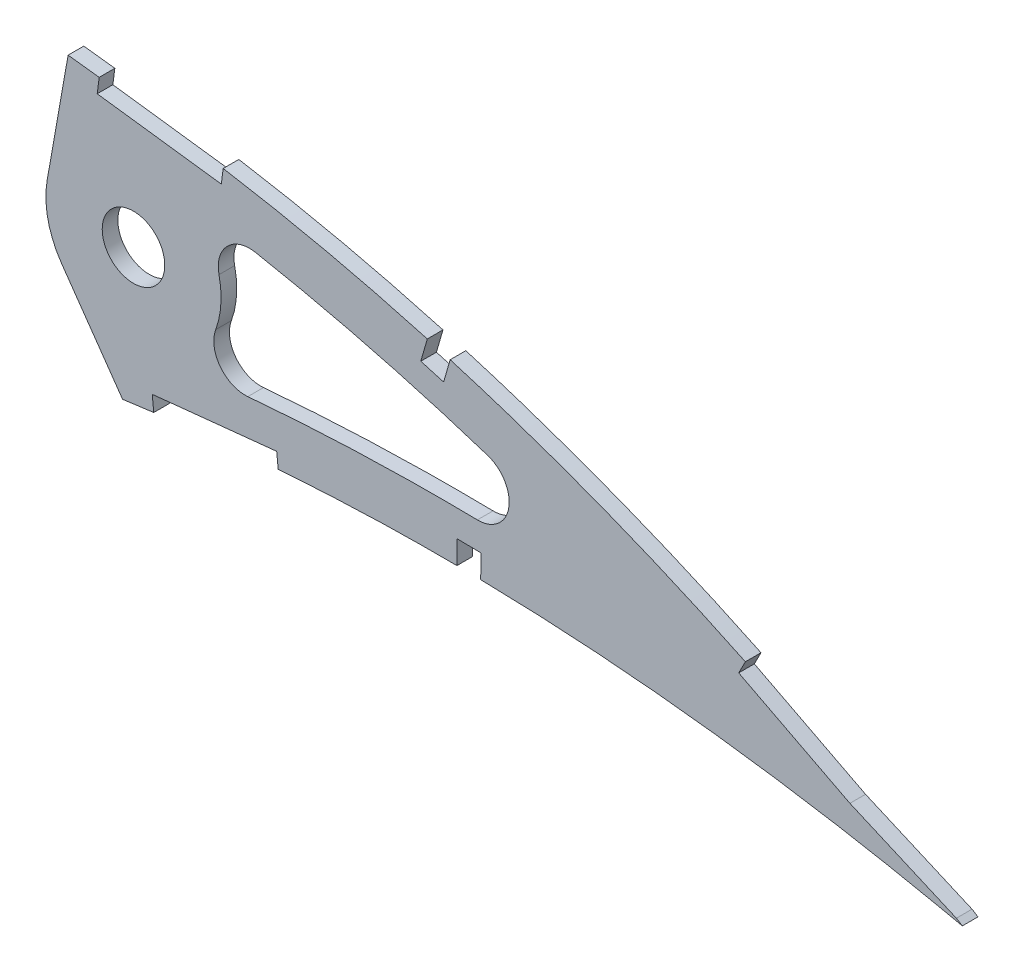
SolidWorks part; units mm, degrees
material "Pine"
ref_plane "Front Plane" through (0, 0, 0) normal (0, 0, 1) x (1, 0, 0)
ref_plane "Top Plane" through (0, 0, 0) normal (0, 1, 0) x (1, 0, 0)
ref_plane "Right Plane" through (0, 0, 0) normal (1, 0, 0) x (0, 0, -1)
curve "Curve1"
  spline degree 3 poles (554.3197, 0.8642, 0) (554.2772, 0.8904, 0) (554.1075, 0.9953, 0) (553.7252, 1.2298, 0) (553.0885, 1.6204, 0) (552.1972, 2.1644, 0) (551.0519, 2.8603, 0) (549.6522, 3.7033, 0) (547.9988, 4.6906, 0) (546.0922, 5.8176, 0) (543.9326, 7.0789, 0) (541.5207, 8.4695, 0) (538.8569, 9.9815, 0) (535.942, 11.6087, 0) (532.7772, 13.3434, 0) (529.3631, 15.1777, 0) (525.7007, 17.1023, 0) (521.7917, 19.109, 0) (517.6366, 21.1866, 0) (513.2374, 23.3265, 0) (508.5956, 25.518, 0) (503.7128, 27.7495, 0) (498.5918, 30.0118, 0) (493.234, 32.2909, 0) (487.6424, 34.577, 0) (481.8195, 36.8569, 0) (475.7686, 39.1203, 0) (469.4922, 41.3526, 0) (462.9949, 43.5439, 0) (456.2798, 45.6802, 0) (449.3518, 47.7496, 0) (442.2149, 49.739, 0) (434.875, 51.6379, 0) (427.3368, 53.4327, 0) (419.6066, 55.1112, 0) (411.6907, 56.6635, 0) (403.5957, 58.0739, 0) (395.344, 59.3415, 0) (387.0683, 60.3958, 0) (378.8096, 61.4299, 0) (370.5633, 62.4014, 0) (362.2161, 63.3317, 0) (353.7762, 64.2156, 0) (345.252, 65.0503, 0) (336.6519, 65.8323, 0) (327.9851, 66.5592, 0) (319.2598, 67.227, 0) (310.4852, 67.8346, 0) (301.6702, 68.3766, 0) (292.8239, 68.8527, 0) (283.9555, 69.2595, 0) (275.0741, 69.5943, 0) (266.1892, 69.8549, 0) (257.3099, 70.039, 0) (248.446, 70.1454, 0) (239.6066, 70.171, 0) (230.8014, 70.1156, 0) (222.0395, 69.9772, 0) (213.3305, 69.7538, 0) (204.6838, 69.4452, 0) (196.1087, 69.0513, 0) (187.6145, 68.5689, 0) (179.2105, 68.0012, 0) (170.9059, 67.3456, 0) (162.7101, 66.6021, 0) (154.6315, 65.7736, 0) (146.6791, 64.8581, 0) (138.8614, 63.858, 0) (131.1871, 62.7754, 0) (123.6647, 61.6096, 0) (116.3022, 60.3641, 0) (109.1077, 59.04, 0) (102.0887, 57.6413, 0) (95.2529, 56.1683, 0) (88.6074, 54.6255, 0) (82.1593, 53.0155, 0) (75.9155, 51.3413, 0) (69.8822, 49.607, 0) (64.0656, 47.8163, 0) (58.4725, 45.9714, 0) (53.107, 44.0792, 0) (47.9758, 42.141, 0) (43.0829, 40.1629, 0) (38.4338, 38.1474, 0) (34.0322, 36.1008, 0) (29.883, 34.0255, 0) (25.9891, 31.9271, 0) (22.3545, 29.809, 0) (18.9827, 27.675, 0) (15.875, 25.5306, 0) (13.0358, 23.3771, 0) (10.4661, 21.22, 0) (8.1674, 19.0625, 0) (6.143, 16.9061, 0) (4.3929, 14.7547, 0) (2.9194, 12.6099, 0) (1.7228, 10.4738, 0) (0.8056, 8.3479, 0) (0.1671, 6.2334, 0) (-0.1824, 4.1334, 0) (-0.2694, 2.0463, 0) (-0.0897, 0.6811, 0) (0, 0, 0) knots 0 0 0 0 0.000254 0.001015 0.002283 0.004057 0.006331 0.009105 0.012374 0.016134 0.02038 0.025106 0.030306 0.035972 0.0421 0.048678 0.055702 0.06316 0.071046 0.07935 0.088063 0.097176 0.106678 0.116562 0.126814 0.137428 0.148394 0.1597 0.171338 0.183298 0.19557 0.208144 0.221012 0.234162 0.247587 0.261277 0.275223 0.289414 0.303771 0.317689 0.331784 0.34604 0.360444 0.374983 0.38964 0.404403 0.419257 0.434187 0.449177 0.464215 0.479284 0.49437 0.509458 0.524532 0.539579 0.554583 0.56953 0.584403 0.599191 0.613877 0.628447 0.642889 0.657186 0.671326 0.685294 0.699078 0.712665 0.726043 0.739198 0.752118 0.764792 0.777208 0.789356 0.801224 0.812804 0.824083 0.835055 0.84571 0.856038 0.866034 0.875689 0.884998 0.893953 0.902553 0.910789 0.918661 0.926166 0.933303 0.940071 0.946475 0.952518 0.958205 0.963547 0.968557 0.97325 0.977651 0.981787 0.985694 0.989415 0.993001 0.996508 1 1 1 1
curve "Curve2"
  spline degree 3 poles (0, 0, 0) (0.1423, -0.672, 0) (0.4277, -2.019, 0) (1.203, -3.9582, 0) (2.2282, -5.8223, 0) (3.5249, -7.6064, 0) (5.0845, -9.31, 0) (6.9036, -10.9348, 0) (8.9803, -12.4801, 0) (11.3119, -13.945, 0) (13.8951, -15.3312, 0) (16.7269, -16.6378, 0) (19.8048, -17.8643, 0) (23.1254, -19.0092, 0) (26.6846, -20.0741, 0) (30.4791, -21.0566, 0) (34.5045, -21.9578, 0) (38.7571, -22.7757, 0) (43.232, -23.5109, 0) (47.9248, -24.1631, 0) (52.8305, -24.7327, 0) (57.9444, -25.2185, 0) (63.2614, -25.6215, 0) (68.7762, -25.942, 0) (74.4834, -26.1811, 0) (80.3777, -26.3377, 0) (86.4531, -26.4144, 0) (92.7043, -26.4123, 0) (99.1251, -26.3308, 0) (105.71, -26.1745, 0) (112.4527, -25.9423, 0) (119.3471, -25.6371, 0) (126.387, -25.2619, 0) (133.5661, -24.818, 0) (140.8781, -24.3074, 0) (148.3166, -23.7341, 0) (155.8748, -23.0997, 0) (163.5462, -22.4077, 0) (171.324, -21.6617, 0) (179.2015, -20.864, 0) (187.1716, -20.0183, 0) (195.2274, -19.1275, 0) (203.3619, -18.1963, 0) (211.5677, -17.2262, 0) (219.8379, -16.223, 0) (228.1647, -15.1885, 0) (236.5412, -14.1266, 0) (244.9597, -13.0425, 0) (253.4125, -11.9359, 0) (261.8924, -10.8148, 0) (270.3912, -9.6781, 0) (278.9016, -8.5319, 0) (287.4156, -7.3796, 0) (295.925, -6.2216, 0) (304.4222, -5.0626, 0) (312.8995, -3.9059, 0) (321.3485, -2.7516, 0) (329.7616, -1.6054, 0) (338.1302, -0.4672, 0) (346.4467, 0.6607, 0) (354.7031, 1.775, 0) (362.8916, 2.8743, 0) (371.0037, 3.9578, 0) (379.0314, 5.0259, 0) (386.8463, 6.0463, 0) (394.4281, 7.0733, 0) (401.8022, 7.9152, 0) (409.0845, 8.6338, 0) (416.2825, 9.2229, 0) (423.3877, 9.6911, 0) (430.3918, 10.0417, 0) (437.2865, 10.2795, 0) (444.0631, 10.4116, 0) (450.7132, 10.4414, 0) (457.2276, 10.3785, 0) (463.598, 10.2277, 0) (469.8153, 9.9961, 0) (475.8709, 9.6912, 0) (481.7563, 9.3216, 0) (487.4626, 8.8925, 0) (492.9818, 8.4141, 0) (498.3055, 7.8933, 0) (503.4254, 7.336, 0) (508.334, 6.7541, 0) (513.0236, 6.1512, 0) (517.4871, 5.5374, 0) (521.7172, 4.9187, 0) (525.7074, 4.3032, 0) (529.4512, 3.6966, 0) (532.9427, 3.1071, 0) (536.1764, 2.5402, 0) (539.1467, 2.0013, 0) (541.8495, 1.4973, 0) (544.2794, 1.0307, 0) (546.4331, 0.6092, 0) (548.3068, 0.2346, 0) (549.8976, -0.0878, 0) (551.2027, -0.3567, 0) (552.2202, -0.5677, 0) (552.948, -0.7211, 0) (553.3854, -0.8124, 0) (553.5798, -0.8538, 0) (553.6283, -0.8642, 0) knots 0 0 0 0 0.003638 0.007293 0.011028 0.014901 0.018963 0.023258 0.027821 0.032679 0.037853 0.043362 0.049215 0.055422 0.061989 0.068918 0.076211 0.083868 0.091887 0.100266 0.109 0.118085 0.127515 0.137285 0.147388 0.157816 0.168563 0.179619 0.190977 0.202627 0.21456 0.226767 0.239236 0.251959 0.264924 0.27812 0.291536 0.30516 0.318981 0.332985 0.347163 0.361499 0.375981 0.390597 0.405333 0.420175 0.43511 0.450124 0.465203 0.480333 0.495501 0.51069 0.525887 0.541078 0.556247 0.571382 0.586466 0.601485 0.616424 0.631269 0.646007 0.660621 0.675098 0.689423 0.703582 0.716908 0.730009 0.742952 0.755726 0.76832 0.780724 0.792927 0.804916 0.816679 0.828204 0.839475 0.850481 0.861208 0.871639 0.881763 0.891564 0.901027 0.910139 0.918884 0.927249 0.935221 0.942785 0.949928 0.956638 0.962904 0.968712 0.974054 0.978918 0.983297 0.98718 0.990561 0.993433 0.995791 0.99763 0.998946 0.999737 1 1 1 1
sketch "Sketch1" plane through (0, 0, 0) normal (0, 0, 1) x (1, 0, 0)
  line L28 (0, 63.5) -> (-23.1981, 63.5) construction
  line L39 (379.9183, -27.3345) -> (379.9183, 27.3345) construction
  line L40 (368.4067, 59.4277) -> (353.2793, 2.9714) construction
  line L41 (537.5238, 0.838) -> (542.0214, -1.9404)
  line L42 (536.8534, -0.838) -> (542.0214, -1.9404)
  circle A0 centre (68.58, 6.35) radius 9.525 construction
  circle A1 centre (246.38, 6.35) radius 9.525 construction
  spline S3 degree 3 poles (0, 0) (0.138, -0.6516) (0.4147, -1.9578) (1.1665, -3.8383) (2.1607, -5.6459) (3.4181, -7.3759) (4.9305, -9.0279) (6.6944, -10.6035) (8.7082, -12.1019) (10.9692, -13.5225) (13.4741, -14.8667) (16.2201, -16.1336) (19.2047, -17.323) (22.4247, -18.4332) (25.8761, -19.4659) (29.5556, -20.4185) (33.4591, -21.2925) (37.5827, -22.0856) (41.9221, -22.7985) (46.4726, -23.431) (51.2297, -23.9833) (56.1887, -24.4544) (61.3446, -24.8452) (66.6923, -25.156) (72.2266, -25.3878) (77.9422, -25.5397) (83.8336, -25.6141) (89.8954, -25.612) (96.1216, -25.533) (102.507, -25.3814) (109.0454, -25.1563) (115.7309, -24.8603) (122.5575, -24.4965) (129.5191, -24.066) (136.6095, -23.5709) (143.8226, -23.015) (151.1518, -22.3997) (158.5908, -21.7287) (166.1329, -21.0053) (173.7717, -20.2318) (181.5003, -19.4118) (189.312, -18.5479) (197.2, -17.6449) (205.1572, -16.7043) (213.1768, -15.7315) (221.2513, -14.7283) (229.374, -13.6986) (237.5374, -12.6473) (245.7341, -11.5743) (253.957, -10.4871) (262.1983, -9.3849) (270.4508, -8.2734) (278.7069, -7.156) (286.9584, -6.033) (295.1983, -4.9092) (303.4187, -3.7876) (311.6117, -2.6683) (319.7698, -1.5568) (327.8848, -0.4531) (335.9493, 0.6407) (343.9556, 1.7212) (351.896, 2.7872) (359.7623, 3.8379) (367.5468, 4.8736) (375.1249, 5.8631) (382.4769, 6.859) (389.6276, 7.6754) (396.6892, 8.3722) (403.6691, 8.9435) (410.559, 9.3975) (417.3509, 9.7374) (424.0367, 9.968) (430.608, 10.0961) (437.0566, 10.1251) (443.3736, 10.064) (449.5509, 9.9178) (455.5799, 9.6932) (461.4521, 9.3976) (467.1591, 9.0391) (472.6925, 8.6231) (478.0445, 8.1591) (483.2068, 7.6541) (488.1716, 7.1138) (492.9315, 6.5494) (497.479, 5.9648) (501.8072, 5.3696) (505.9092, 4.7697) (509.7784, 4.1728) (513.4088, 3.5846) (516.7946, 3.013) (519.9303, 2.4632) (522.8106, 1.9407) (525.4315, 1.4519) (527.7877, 0.9995) (529.8762, 0.5907) (531.6931, 0.2275) (533.2357, -0.0851) (534.5012, -0.3459) (535.4879, -0.5505) (536.1937, -0.6992) (536.6178, -0.7878) (536.8063, -0.828) (536.8534, -0.838) knots 0 0 0 0 0.003638 0.007293 0.011028 0.014901 0.018963 0.023258 0.027821 0.032679 0.037853 0.043362 0.049215 0.055422 0.061989 0.068918 0.076211 0.083868 0.091887 0.100266 0.109 0.118085 0.127515 0.137285 0.147388 0.157816 0.168563 0.179619 0.190977 0.202627 0.21456 0.226767 0.239236 0.251959 0.264924 0.27812 0.291536 0.30516 0.318981 0.332985 0.347163 0.361499 0.375981 0.390597 0.405333 0.420175 0.43511 0.450124 0.465203 0.480333 0.495501 0.51069 0.525887 0.541078 0.556247 0.571382 0.586466 0.601485 0.616424 0.631269 0.646007 0.660621 0.675098 0.689423 0.703582 0.716908 0.730009 0.742952 0.755726 0.76832 0.780724 0.792927 0.804916 0.816679 0.828204 0.839475 0.850481 0.861208 0.871639 0.881763 0.891564 0.901027 0.910139 0.918884 0.927249 0.935221 0.942785 0.949928 0.956638 0.962904 0.968712 0.974054 0.978918 0.983297 0.98718 0.990561 0.993433 0.995791 0.99763 0.998946 0.999737 1 1 1 1
  spline S6 degree 3 poles (537.5238, 0.838) (537.4826, 0.8635) (537.3181, 0.9651) (536.9473, 1.1925) (536.3299, 1.5713) (535.4656, 2.0988) (534.3551, 2.7737) (532.9977, 3.5911) (531.3944, 4.5485) (529.5456, 5.6413) (527.4514, 6.8644) (525.1126, 8.2129) (522.5295, 9.6791) (519.703, 11.2569) (516.6341, 12.9391) (513.3234, 14.7178) (509.772, 16.5841) (505.9814, 18.53) (501.9522, 20.5446) (497.6863, 22.6197) (493.1852, 24.7448) (488.4503, 26.9087) (483.4845, 29.1025) (478.289, 31.3125) (472.8669, 33.5293) (467.2204, 35.7401) (461.3528, 37.9349) (455.2666, 40.0996) (448.9661, 42.2246) (442.4545, 44.296) (435.7364, 46.3028) (428.8157, 48.2319) (421.6983, 50.0733) (414.3885, 51.8137) (406.8926, 53.4414) (399.2165, 54.9466) (391.3668, 56.3143) (383.365, 57.5434) (375.3401, 58.5658) (367.3317, 59.5686) (359.3352, 60.5106) (351.241, 61.4127) (343.0568, 62.2698) (334.7908, 63.0793) (326.4514, 63.8376) (318.0471, 64.5425) (309.5862, 65.19) (301.0775, 65.7792) (292.5296, 66.3048) (283.9513, 66.7665) (275.3516, 67.161) (266.7393, 67.4856) (258.1236, 67.7383) (249.5134, 67.9168) (240.9181, 68.0199) (232.3465, 68.0449) (223.8081, 67.9911) (215.3117, 67.8569) (206.8666, 67.6403) (198.4819, 67.341) (190.1666, 66.959) (181.9298, 66.4913) (173.7804, 65.9407) (165.7275, 65.305) (157.78, 64.584) (149.9461, 63.7807) (142.2347, 62.8929) (134.6539, 61.9231) (127.2121, 60.8733) (119.9176, 59.7429) (112.7783, 58.535) (105.8017, 57.2511) (98.9954, 55.8947) (92.3667, 54.4664) (85.9226, 52.9703) (79.6699, 51.4091) (73.6153, 49.7857) (67.7648, 48.1039) (62.1244, 46.3675) (56.7008, 44.5785) (51.4979, 42.7436) (46.5222, 40.8641) (41.7775, 38.9459) (37.2693, 36.9916) (33.0011, 35.007) (28.9776, 32.9945) (25.2017, 30.9597) (21.6772, 28.9058) (18.4075, 26.8364) (15.394, 24.757) (12.6408, 22.6688) (10.1489, 20.577) (7.9199, 18.4849) (5.9569, 16.3939) (4.2598, 14.3076) (2.831, 12.2278) (1.6706, 10.1565) (0.7812, 8.095) (0.162, 6.0445) (-0.1769, 4.0082) (-0.2612, 1.9843) (-0.087, 0.6604) (0, 0) knots 0 0 0 0 0.000254 0.001015 0.002283 0.004057 0.006331 0.009105 0.012374 0.016134 0.02038 0.025106 0.030306 0.035972 0.0421 0.048678 0.055702 0.06316 0.071046 0.07935 0.088063 0.097176 0.106678 0.116562 0.126814 0.137428 0.148394 0.1597 0.171338 0.183298 0.19557 0.208144 0.221012 0.234162 0.247587 0.261277 0.275223 0.289414 0.303771 0.317689 0.331784 0.34604 0.360444 0.374983 0.38964 0.404403 0.419257 0.434187 0.449177 0.464215 0.479284 0.49437 0.509458 0.524532 0.539579 0.554583 0.56953 0.584403 0.599191 0.613877 0.628447 0.642889 0.657186 0.671326 0.685294 0.699078 0.712665 0.726043 0.739198 0.752118 0.764792 0.777208 0.789356 0.801224 0.812804 0.824083 0.835055 0.84571 0.856038 0.866034 0.875689 0.884998 0.893953 0.902553 0.910789 0.918661 0.926166 0.933303 0.940071 0.946475 0.952518 0.958205 0.963547 0.968557 0.97325 0.977651 0.981787 0.985694 0.989415 0.993001 0.996508 1 1 1 1
  point P10 (78.5929, 16.5948)
  point P11 (227.8303, 32.4941)
  dimension "D2" = 19.05
  dimension "D18" = 177.8
  dimension "D3" = 15
  dimension "D5" = 63.5
  dimension "D7" = 57.15
  dimension "D12" = 57.15
  dimension "D17" = 68.58
extrude "Boss-Extrude1" add sketch "Sketch1" along normal blind 3.175
sketch "Sketch4" plane through (0, 0, 0) normal (0, 0, -1) x (-1, 0, 0)
  line L0 (-356.287, 36.32) -> (-360.5267, 60.365)
  line L1 (-359.2323, 23.0344) -> (-371.5795, 5.4008)
  line L2 (-373.7968, 33.2326) -> (-412.6852, 33.2326)
  circle A0 centre (-373.7968, 33.2326) radius 17.78
  circle A1 centre (-373.7968, 33.2326) radius 6.35
  spline S0 degree 3 poles (-1632.0302, 1674.0962) (-565.4284, -22.6918) (-552.7247, -8.4851) (-536.9473, 1.1925) (-536.3299, 1.5713) (-535.4656, 2.0988) (-534.3551, 2.7737) (-532.9977, 3.5911) (-531.3944, 4.5485) (-529.5456, 5.6413) (-527.4514, 6.8644) (-525.1126, 8.2129) (-522.5295, 9.6791) (-519.703, 11.2569) (-516.6341, 12.9391) (-513.3234, 14.7178) (-509.772, 16.5841) (-505.9814, 18.53) (-501.9522, 20.5446) (-497.6863, 22.6197) (-493.1852, 24.7448) (-488.4503, 26.9087) (-483.4845, 29.1025) (-478.289, 31.3125) (-472.8669, 33.5293) (-467.2204, 35.7401) (-461.3528, 37.9349) (-455.2666, 40.0996) (-448.9661, 42.2246) (-442.4545, 44.296) (-435.7364, 46.3028) (-428.8157, 48.2319) (-421.6983, 50.0733) (-414.3885, 51.8137) (-406.8926, 53.4414) (-399.2165, 54.9466) (-391.3668, 56.3143) (-383.365, 57.5434) (-375.3401, 58.5658) (-367.3317, 59.5686) (-359.3352, 60.5106) (-351.241, 61.4127) (-343.0568, 62.2698) (-334.7908, 63.0793) (-326.4514, 63.8376) (-318.0471, 64.5425) (-309.5862, 65.19) (-301.0775, 65.7792) (-292.5296, 66.3048) (-283.9513, 66.7665) (-275.3516, 67.161) (-266.7393, 67.4856) (-258.1236, 67.7383) (-249.5134, 67.9168) (-240.9181, 68.0199) (-232.3465, 68.0449) (-223.8081, 67.9911) (-215.3117, 67.8569) (-206.8666, 67.6403) (-198.4819, 67.341) (-190.1666, 66.959) (-181.9298, 66.4913) (-173.7804, 65.9407) (-165.7275, 65.305) (-157.78, 64.584) (-149.9461, 63.7807) (-142.2347, 62.8929) (-134.6539, 61.9231) (-127.2121, 60.8733) (-119.9176, 59.7429) (-112.7783, 58.535) (-105.8017, 57.2511) (-98.9954, 55.8947) (-92.3667, 54.4664) (-85.9226, 52.9703) (-79.6699, 51.4091) (-73.6153, 49.7857) (-67.7648, 48.1039) (-62.1244, 46.3675) (-56.7008, 44.5785) (-51.4979, 42.7436) (-46.5222, 40.8641) (-41.7775, 38.9459) (-37.2693, 36.9916) (-33.0011, 35.007) (-28.9776, 32.9945) (-25.2017, 30.9597) (-21.6772, 28.9058) (-18.4075, 26.8364) (-15.394, 24.757) (-12.6408, 22.6688) (-10.1489, 20.577) (-7.9199, 18.4849) (-5.9569, 16.3939) (-4.2598, 14.3076) (-2.831, 12.2278) (-1.6706, 10.1565) (-0.7812, 8.095) (-0.162, 6.0445) (0.1769, 4.0082) (1.1707, -19.8347) (-66.7598, -38.6935) (1990.434, -189.4699) knots -0.094882 -0.094882 -0.094882 -0.094882 0.000254 0.001015 0.002283 0.004057 0.006331 0.009105 0.012374 0.016134 0.02038 0.025106 0.030306 0.035972 0.0421 0.048678 0.055702 0.06316 0.071046 0.07935 0.088063 0.097176 0.106678 0.116562 0.126814 0.137428 0.148394 0.1597 0.171338 0.183298 0.19557 0.208144 0.221012 0.234162 0.247587 0.261277 0.275223 0.289414 0.303771 0.317689 0.331784 0.34604 0.360444 0.374983 0.38964 0.404403 0.419257 0.434187 0.449177 0.464215 0.479284 0.49437 0.509458 0.524532 0.539579 0.554583 0.56953 0.584403 0.599191 0.613877 0.628447 0.642889 0.657186 0.671326 0.685294 0.699078 0.712665 0.726043 0.739198 0.752118 0.764792 0.777208 0.789356 0.801224 0.812804 0.824083 0.835055 0.84571 0.856038 0.866034 0.875689 0.884998 0.893953 0.902553 0.910789 0.918661 0.926166 0.933303 0.940071 0.946475 0.952518 0.958205 0.963547 0.968557 0.97325 0.977651 0.981787 0.985694 0.989415 0.993001 0.996508 1.114113 1.114113 1.114113 1.114113 only from (-537.5238, 0.838) to (0, 0) construction
  spline S1 degree 3 poles (1940.1203, -483.4322) (-49.9299, 58.7424) (7.7069, 18.357) (-1.1665, -3.8383) (-2.1607, -5.6459) (-3.4181, -7.3759) (-4.9305, -9.0279) (-6.6944, -10.6035) (-8.7082, -12.1019) (-10.9692, -13.5225) (-13.4741, -14.8667) (-16.2201, -16.1336) (-19.2047, -17.323) (-22.4247, -18.4332) (-25.8761, -19.4659) (-29.5556, -20.4185) (-33.4591, -21.2925) (-37.5827, -22.0856) (-41.9221, -22.7985) (-46.4726, -23.431) (-51.2297, -23.9833) (-56.1887, -24.4544) (-61.3446, -24.8452) (-66.6923, -25.156) (-72.2266, -25.3878) (-77.9422, -25.5397) (-83.8336, -25.6141) (-89.8954, -25.612) (-96.1216, -25.533) (-102.507, -25.3814) (-109.0454, -25.1563) (-115.7309, -24.8603) (-122.5575, -24.4965) (-129.5191, -24.066) (-136.6095, -23.5709) (-143.8226, -23.015) (-151.1518, -22.3997) (-158.5908, -21.7287) (-166.1329, -21.0053) (-173.7717, -20.2318) (-181.5003, -19.4118) (-189.312, -18.5479) (-197.2, -17.6449) (-205.1572, -16.7043) (-213.1768, -15.7315) (-221.2513, -14.7283) (-229.374, -13.6986) (-237.5374, -12.6473) (-245.7341, -11.5743) (-253.957, -10.4871) (-262.1983, -9.3849) (-270.4508, -8.2734) (-278.7069, -7.156) (-286.9584, -6.033) (-295.1983, -4.9092) (-303.4187, -3.7876) (-311.6117, -2.6683) (-319.7698, -1.5568) (-327.8848, -0.4531) (-335.9493, 0.6407) (-343.9556, 1.7212) (-351.896, 2.7872) (-359.7623, 3.8379) (-367.5468, 4.8736) (-375.1249, 5.8631) (-382.4769, 6.859) (-389.6276, 7.6754) (-396.6892, 8.3722) (-403.6691, 8.9435) (-410.559, 9.3975) (-417.3509, 9.7374) (-424.0367, 9.968) (-430.608, 10.0961) (-437.0566, 10.1251) (-443.3736, 10.064) (-449.5509, 9.9178) (-455.5799, 9.6932) (-461.4521, 9.3976) (-467.1591, 9.0391) (-472.6925, 8.6231) (-478.0445, 8.1591) (-483.2068, 7.6541) (-488.1716, 7.1138) (-492.9315, 6.5494) (-497.479, 5.9648) (-501.8072, 5.3696) (-505.9092, 4.7697) (-509.7784, 4.1728) (-513.4088, 3.5846) (-516.7946, 3.013) (-519.9303, 2.4632) (-522.8106, 1.9407) (-525.4315, 1.4519) (-527.7877, 0.9995) (-529.8762, 0.5907) (-531.6931, 0.2275) (-533.2357, -0.0851) (-534.5012, -0.3459) (-535.4879, -0.5505) (-536.1937, -0.6992) (-552.4366, -4.0895) (-567.1821, -13.3973) (-997.8539, 1944.6618) knots -0.119141 -0.119141 -0.119141 -0.119141 0.003638 0.007293 0.011028 0.014901 0.018963 0.023258 0.027821 0.032679 0.037853 0.043362 0.049215 0.055422 0.061989 0.068918 0.076211 0.083868 0.091887 0.100266 0.109 0.118085 0.127515 0.137285 0.147388 0.157816 0.168563 0.179619 0.190977 0.202627 0.21456 0.226767 0.239236 0.251959 0.264924 0.27812 0.291536 0.30516 0.318981 0.332985 0.347163 0.361499 0.375981 0.390597 0.405333 0.420175 0.43511 0.450124 0.465203 0.480333 0.495501 0.51069 0.525887 0.541078 0.556247 0.571382 0.586466 0.601485 0.616424 0.631269 0.646007 0.660621 0.675098 0.689423 0.703582 0.716908 0.730009 0.742952 0.755726 0.76832 0.780724 0.792927 0.804916 0.816679 0.828204 0.839475 0.850481 0.861208 0.871639 0.881763 0.891564 0.901027 0.910139 0.918884 0.927249 0.935221 0.942785 0.949928 0.956638 0.962904 0.968712 0.974054 0.978918 0.983297 0.98718 0.990561 0.993433 0.995791 0.99763 0.998946 0.999737 1.088404 1.088404 1.088404 1.088404 only from (0, 0) to (-536.8534, -0.838) construction
  spline S2 degree 3 poles (-537.5238, 0.838) (-537.4826, 0.8635) (-537.3181, 0.9651) (-536.9473, 1.1925) (-536.3299, 1.5713) (-535.4656, 2.0988) (-534.3551, 2.7737) (-532.9977, 3.5911) (-531.3944, 4.5485) (-529.5456, 5.6413) (-527.4514, 6.8644) (-525.1126, 8.2129) (-522.5295, 9.6791) (-519.703, 11.2569) (-516.6341, 12.9391) (-513.3234, 14.7178) (-509.772, 16.5841) (-505.9814, 18.53) (-501.9522, 20.5446) (-497.6863, 22.6197) (-493.1852, 24.7448) (-488.4503, 26.9087) (-483.4845, 29.1025) (-478.289, 31.3125) (-472.8669, 33.5293) (-467.2204, 35.7401) (-461.3528, 37.9349) (-455.2666, 40.0996) (-448.9661, 42.2246) (-442.4545, 44.296) (-435.7364, 46.3028) (-428.8157, 48.2319) (-421.6983, 50.0733) (-414.3885, 51.8137) (-406.8926, 53.4414) (-399.2165, 54.9466) (-391.3668, 56.3143) (-383.365, 57.5434) (-375.3401, 58.5658) (-367.3317, 59.5686) (-359.3352, 60.5106) (-351.241, 61.4127) (-343.0568, 62.2698) (-334.7908, 63.0793) (-326.4514, 63.8376) (-318.0471, 64.5425) (-309.5862, 65.19) (-301.0775, 65.7792) (-292.5296, 66.3048) (-283.9513, 66.7665) (-275.3516, 67.161) (-266.7393, 67.4856) (-258.1236, 67.7383) (-249.5134, 67.9168) (-240.9181, 68.0199) (-232.3465, 68.0449) (-223.8081, 67.9911) (-215.3117, 67.8569) (-206.8666, 67.6403) (-198.4819, 67.341) (-190.1666, 66.959) (-181.9298, 66.4913) (-173.7804, 65.9407) (-165.7275, 65.305) (-157.78, 64.584) (-149.9461, 63.7807) (-142.2347, 62.8929) (-134.6539, 61.9231) (-127.2121, 60.8733) (-119.9176, 59.7429) (-112.7783, 58.535) (-105.8017, 57.2511) (-98.9954, 55.8947) (-92.3667, 54.4664) (-85.9226, 52.9703) (-79.6699, 51.4091) (-73.6153, 49.7857) (-67.7648, 48.1039) (-62.1244, 46.3675) (-56.7008, 44.5785) (-51.4979, 42.7436) (-46.5222, 40.8641) (-41.7775, 38.9459) (-37.2693, 36.9916) (-33.0011, 35.007) (-28.9776, 32.9945) (-25.2017, 30.9597) (-21.6772, 28.9058) (-18.4075, 26.8364) (-15.394, 24.757) (-12.6408, 22.6688) (-10.1489, 20.577) (-7.9199, 18.4849) (-5.9569, 16.3939) (-4.2598, 14.3076) (-2.831, 12.2278) (-1.6706, 10.1565) (-0.7812, 8.095) (-0.162, 6.0445) (0.1769, 4.0082) (0.2612, 1.9843) (0.087, 0.6604) (0, 0) knots 0 0 0 0 0.000254 0.001015 0.002283 0.004057 0.006331 0.009105 0.012374 0.016134 0.02038 0.025106 0.030306 0.035972 0.0421 0.048678 0.055702 0.06316 0.071046 0.07935 0.088063 0.097176 0.106678 0.116562 0.126814 0.137428 0.148394 0.1597 0.171338 0.183298 0.19557 0.208144 0.221012 0.234162 0.247587 0.261277 0.275223 0.289414 0.303771 0.317689 0.331784 0.34604 0.360444 0.374983 0.38964 0.404403 0.419257 0.434187 0.449177 0.464215 0.479284 0.49437 0.509458 0.524532 0.539579 0.554583 0.56953 0.584403 0.599191 0.613877 0.628447 0.642889 0.657186 0.671326 0.685294 0.699078 0.712665 0.726043 0.739198 0.752118 0.764792 0.777208 0.789356 0.801224 0.812804 0.824083 0.835055 0.84571 0.856038 0.866034 0.875689 0.884998 0.893953 0.902553 0.910789 0.918661 0.926166 0.933303 0.940071 0.946475 0.952518 0.958205 0.963547 0.968557 0.97325 0.977651 0.981787 0.985694 0.989415 0.993001 0.996508 1 1 1 1
  spline S3 degree 3 poles (0, 0) (-0.138, -0.6516) (-0.4147, -1.9578) (-1.1665, -3.8383) (-2.1607, -5.6459) (-3.4181, -7.3759) (-4.9305, -9.0279) (-6.6944, -10.6035) (-8.7082, -12.1019) (-10.9692, -13.5225) (-13.4741, -14.8667) (-16.2201, -16.1336) (-19.2047, -17.323) (-22.4247, -18.4332) (-25.8761, -19.4659) (-29.5556, -20.4185) (-33.4591, -21.2925) (-37.5827, -22.0856) (-41.9221, -22.7985) (-46.4726, -23.431) (-51.2297, -23.9833) (-56.1887, -24.4544) (-61.3446, -24.8452) (-66.6923, -25.156) (-72.2266, -25.3878) (-77.9422, -25.5397) (-83.8336, -25.6141) (-89.8954, -25.612) (-96.1216, -25.533) (-102.507, -25.3814) (-109.0454, -25.1563) (-115.7309, -24.8603) (-122.5575, -24.4965) (-129.5191, -24.066) (-136.6095, -23.5709) (-143.8226, -23.015) (-151.1518, -22.3997) (-158.5908, -21.7287) (-166.1329, -21.0053) (-173.7717, -20.2318) (-181.5003, -19.4118) (-189.312, -18.5479) (-197.2, -17.6449) (-205.1572, -16.7043) (-213.1768, -15.7315) (-221.2513, -14.7283) (-229.374, -13.6986) (-237.5374, -12.6473) (-245.7341, -11.5743) (-253.957, -10.4871) (-262.1983, -9.3849) (-270.4508, -8.2734) (-278.7069, -7.156) (-286.9584, -6.033) (-295.1983, -4.9092) (-303.4187, -3.7876) (-311.6117, -2.6683) (-319.7698, -1.5568) (-327.8848, -0.4531) (-335.9493, 0.6407) (-343.9556, 1.7212) (-351.896, 2.7872) (-359.7623, 3.8379) (-367.5468, 4.8736) (-375.1249, 5.8631) (-382.4769, 6.859) (-389.6276, 7.6754) (-396.6892, 8.3722) (-403.6691, 8.9435) (-410.559, 9.3975) (-417.3509, 9.7374) (-424.0367, 9.968) (-430.608, 10.0961) (-437.0566, 10.1251) (-443.3736, 10.064) (-449.5509, 9.9178) (-455.5799, 9.6932) (-461.4521, 9.3976) (-467.1591, 9.0391) (-472.6925, 8.6231) (-478.0445, 8.1591) (-483.2068, 7.6541) (-488.1716, 7.1138) (-492.9315, 6.5494) (-497.479, 5.9648) (-501.8072, 5.3696) (-505.9092, 4.7697) (-509.7784, 4.1728) (-513.4088, 3.5846) (-516.7946, 3.013) (-519.9303, 2.4632) (-522.8106, 1.9407) (-525.4315, 1.4519) (-527.7877, 0.9995) (-529.8762, 0.5907) (-531.6931, 0.2275) (-533.2357, -0.0851) (-534.5012, -0.3459) (-535.4879, -0.5505) (-536.1937, -0.6992) (-536.6178, -0.7878) (-536.8063, -0.828) (-536.8534, -0.838) knots 0 0 0 0 0.003638 0.007293 0.011028 0.014901 0.018963 0.023258 0.027821 0.032679 0.037853 0.043362 0.049215 0.055422 0.061989 0.068918 0.076211 0.083868 0.091887 0.100266 0.109 0.118085 0.127515 0.137285 0.147388 0.157816 0.168563 0.179619 0.190977 0.202627 0.21456 0.226767 0.239236 0.251959 0.264924 0.27812 0.291536 0.30516 0.318981 0.332985 0.347163 0.361499 0.375981 0.390597 0.405333 0.420175 0.43511 0.450124 0.465203 0.480333 0.495501 0.51069 0.525887 0.541078 0.556247 0.571382 0.586466 0.601485 0.616424 0.631269 0.646007 0.660621 0.675098 0.689423 0.703582 0.716908 0.730009 0.742952 0.755726 0.76832 0.780724 0.792927 0.804916 0.816679 0.828204 0.839475 0.850481 0.861208 0.871639 0.881763 0.891564 0.901027 0.910139 0.918884 0.927249 0.935221 0.942785 0.949928 0.956638 0.962904 0.968712 0.974054 0.978918 0.983297 0.98718 0.990561 0.993433 0.995791 0.99763 0.998946 0.999737 1 1 1 1
  spline S4 degree 1 poles (-532.1841, -7.8057) (-10.0219, 1.7185) knots 0 0 1 1 construction
  spline S5 degree 1 poles (-10.0219, 1.7185) (-538.9729, 9.0984) knots 0 0 1 1 construction
  spline S6 degree 3 poles (-532.1841, -7.8057) (-532.035, -7.7136) (-531.7436, -7.5345) (-531.1023, -7.1412) (-530.0303, -6.4862) (-527.85, -5.1645) (-523.4829, -2.5651) (-514.6678, 2.5066) (-496.7411, 12.095) (-470.3238, 24.1396) (-442.9694, 33.791) (-420.6386, 39.9785) (-406.5149, 43.1961) (-395.1531, 45.3637) (-386.5599, 46.8051) (-378.0384, 47.9972) (-369.1749, 49.1011) (-360.4166, 50.162) (-348.6799, 51.484) (-328.147, 53.5808) (-298.749, 55.9238) (-263.4315, 57.6196) (-228.1119, 58.0844) (-192.8506, 57.171) (-157.7356, 54.6709) (-128.7085, 51.0365) (-105.7459, 46.987) (-88.7097, 43.306) (-71.9299, 38.8842) (-58.261, 34.4734) (-47.6305, 30.4115) (-39.8596, 27.063) (-32.3674, 23.3733) (-25.2794, 19.2928) (-18.8179, 14.7781) (-14.319, 10.6534) (-11.7187, 7.3378) (-10.6606, 5.4268) (-10.2382, 4.2645) (-10.0884, 3.6968) (-10.0101, 3.295) (-9.9553, 2.8496) (-9.9432, 2.5723) (-9.9453, 2.4518) (-9.9493, 2.3713) (-9.9688, 2.1598) (-9.9949, 1.9339) (-10.0132, 1.7875) (-10.0219, 1.7185) knots 0 0 0 0 0.000976 0.001952 0.003903 0.007807 0.015613 0.031226 0.062452 0.124904 0.187357 0.218583 0.249809 0.265422 0.281035 0.296648 0.312261 0.327874 0.343487 0.374713 0.437166 0.499618 0.56207 0.624522 0.686974 0.749427 0.780653 0.811879 0.843105 0.874331 0.889944 0.905557 0.92117 0.936783 0.952396 0.968009 0.975816 0.983623 0.987526 0.989477 0.991429 0.993381 0.995332 0.996308 0.997284 0.99826 0.998748 0.999236 0.999236 0.999236 0.999236
  spline S7 degree 3 poles (-10.0219, 1.7185) (-10.0361, 1.6529) (-10.0665, 1.5144) (-10.1157, 1.2979) (-10.1669, 1.0931) (-10.1938, 1.0009) (-10.2267, 0.9008) (-10.3197, 0.6625) (-10.5705, 0.1458) (-10.9157, -0.4199) (-11.7404, -1.469) (-13.2635, -2.8937) (-16.5705, -5.1355) (-21.8641, -7.6046) (-29.0738, -9.8943) (-36.7462, -11.652) (-44.6834, -12.9788) (-52.7844, -13.9626) (-63.7273, -14.8945) (-77.583, -15.4719) (-94.3476, -15.4772) (-111.1866, -14.9569) (-133.6938, -13.7131) (-161.8825, -11.3422) (-195.7357, -7.6685) (-229.6092, -3.472) (-263.4966, 1.0208) (-297.4142, 5.6457) (-325.6956, 9.51) (-345.5133, 12.184) (-356.8358, 13.6973) (-363.916, 14.6412) (-369.594, 15.387) (-373.812, 15.9419) (-378.0525, 16.5127) (-382.4211, 17.0728) (-386.7861, 17.5755) (-392.5828, 18.1876) (-402.7738, 19.115) (-417.3468, 20.0031) (-440.7096, 20.5101) (-469.8877, 19.4483) (-498.8731, 16.2543) (-518.9745, 12.9996) (-528.9918, 11.1265) (-533.6061, 10.2081) (-535.7587, 9.7686) (-536.8071, 9.5524) (-537.7352, 9.359) (-538.3978, 9.2197) (-538.786, 9.1383) (-538.9729, 9.0984) knots 0.000796 0.000796 0.000796 0.000796 0.001284 0.001772 0.002748 0.003724 0.004699 0.006651 0.008603 0.012506 0.016409 0.024215 0.032021 0.047634 0.063247 0.078859 0.094472 0.110084 0.125697 0.156922 0.188147 0.219372 0.250597 0.313047 0.375498 0.437948 0.500398 0.562848 0.625299 0.656524 0.672136 0.687749 0.695555 0.703361 0.711168 0.718974 0.72678 0.734587 0.750199 0.781424 0.812649 0.8751 0.93755 0.968775 0.984387 0.992194 0.994145 0.996097 0.998048 0.999024 1 1 1 1
  spline M11 degree 3 poles (0, 0) (0.087, 0.6604) (0.2612, 1.9843) (0.1769, 4.0082) (-0.162, 6.0445) (-0.7812, 8.095) (-1.6706, 10.1565) (-2.831, 12.2278) (-4.2598, 14.3076) (-5.9569, 16.3939) (-7.9199, 18.4849) (-10.1489, 20.577) (-12.6408, 22.6688) (-15.394, 24.757) (-18.4075, 26.8364) (-21.6772, 28.9058) (-25.2017, 30.9597) (-28.9776, 32.9945) (-33.0011, 35.007) (-37.2693, 36.9916) (-41.7775, 38.9459) (-46.5222, 40.8641) (-51.4979, 42.7436) (-56.7008, 44.5785) (-62.1244, 46.3675) (-67.7648, 48.1039) (-73.6153, 49.7857) (-79.6699, 51.4091) (-85.9226, 52.9703) (-92.3667, 54.4664) (-98.9954, 55.8947) (-105.8017, 57.2511) (-112.7783, 58.535) (-119.9176, 59.7429) (-127.2121, 60.8733) (-134.6539, 61.9231) (-142.2347, 62.8929) (-149.9461, 63.7807) (-157.78, 64.584) (-165.7275, 65.305) (-173.7804, 65.9407) (-181.9298, 66.4913) (-190.1666, 66.959) (-198.4819, 67.341) (-206.8666, 67.6403) (-215.3117, 67.8569) (-223.8081, 67.9911) (-232.3465, 68.0449) (-240.9181, 68.0199) (-249.5134, 67.9168) (-258.1236, 67.7383) (-266.7393, 67.4856) (-275.3516, 67.161) (-283.9513, 66.7665) (-292.5296, 66.3048) (-301.0775, 65.7792) (-309.5862, 65.19) (-318.0471, 64.5425) (-326.4514, 63.8376) (-334.7908, 63.0793) (-343.0568, 62.2698) (-351.241, 61.4127) (-359.3352, 60.5106) (-367.3317, 59.5686) (-375.3401, 58.5658) (-383.365, 57.5434) (-391.3668, 56.3143) (-399.2165, 54.9466) (-406.8926, 53.4414) (-414.3885, 51.8137) (-421.6983, 50.0733) (-428.8157, 48.2319) (-435.7364, 46.3028) (-442.4545, 44.296) (-448.9661, 42.2246) (-455.2666, 40.0996) (-461.3528, 37.9349) (-467.2204, 35.7401) (-472.8669, 33.5293) (-478.289, 31.3125) (-483.4845, 29.1025) (-488.4503, 26.9087) (-493.1852, 24.7448) (-497.6863, 22.6197) (-501.9522, 20.5446) (-505.9814, 18.53) (-509.772, 16.5841) (-513.3234, 14.7178) (-516.6341, 12.9391) (-519.703, 11.2569) (-522.5295, 9.6791) (-525.1126, 8.2129) (-527.4514, 6.8644) (-529.5456, 5.6413) (-531.3944, 4.5485) (-532.9977, 3.5911) (-534.3551, 2.7737) (-535.4656, 2.0988) (-536.3299, 1.5713) (-536.9473, 1.1925) (-537.3181, 0.9651) (-537.4826, 0.8635) (-537.5238, 0.838) knots 0 0 0 0 0.003492 0.006999 0.010585 0.014306 0.018213 0.022349 0.02675 0.031443 0.036453 0.041795 0.047482 0.053525 0.059929 0.066697 0.073834 0.081339 0.089211 0.097447 0.106047 0.115002 0.124311 0.133966 0.143962 0.15429 0.164945 0.175917 0.187196 0.198776 0.210644 0.222792 0.235208 0.247882 0.260802 0.273957 0.287335 0.300922 0.314706 0.328674 0.342814 0.357111 0.371553 0.386123 0.400809 0.415597 0.43047 0.445417 0.460421 0.475468 0.490542 0.50563 0.520716 0.535785 0.550823 0.565813 0.580743 0.595597 0.61036 0.625017 0.639556 0.65396 0.668216 0.682311 0.696229 0.710586 0.724777 0.738723 0.752413 0.765838 0.778988 0.791856 0.80443 0.816702 0.828662 0.8403 0.851606 0.862572 0.873186 0.883438 0.893322 0.902824 0.911937 0.92065 0.928954 0.93684 0.944298 0.951322 0.9579 0.964028 0.969694 0.974894 0.97962 0.983866 0.987626 0.990895 0.993669 0.995943 0.997717 0.998985 0.999746 1 1 1 1
  spline M14 degree 3 poles (-536.8534, -0.838) (-536.8063, -0.828) (-536.6178, -0.7878) (-536.1937, -0.6992) (-535.4879, -0.5505) (-534.5012, -0.3459) (-533.2357, -0.0851) (-531.6931, 0.2275) (-529.8762, 0.5907) (-527.7877, 0.9995) (-525.4315, 1.4519) (-522.8106, 1.9407) (-519.9303, 2.4632) (-516.7946, 3.013) (-513.4088, 3.5846) (-509.7784, 4.1728) (-505.9092, 4.7697) (-501.8072, 5.3696) (-497.479, 5.9648) (-492.9315, 6.5494) (-488.1716, 7.1138) (-483.2068, 7.6541) (-478.0445, 8.1591) (-472.6925, 8.6231) (-467.1591, 9.0391) (-461.4521, 9.3976) (-455.5799, 9.6932) (-449.5509, 9.9178) (-443.3736, 10.064) (-437.0566, 10.1251) (-430.608, 10.0961) (-424.0367, 9.968) (-417.3509, 9.7374) (-410.559, 9.3975) (-403.6691, 8.9435) (-396.6892, 8.3722) (-389.6276, 7.6754) (-382.4769, 6.859) (-375.1249, 5.8631) (-367.5468, 4.8736) (-359.7623, 3.8379) (-351.896, 2.7872) (-343.9556, 1.7212) (-335.9493, 0.6407) (-327.8848, -0.4531) (-319.7698, -1.5568) (-311.6117, -2.6683) (-303.4187, -3.7876) (-295.1983, -4.9092) (-286.9584, -6.033) (-278.7069, -7.156) (-270.4508, -8.2734) (-262.1983, -9.3849) (-253.957, -10.4871) (-245.7341, -11.5743) (-237.5374, -12.6473) (-229.374, -13.6986) (-221.2513, -14.7283) (-213.1768, -15.7315) (-205.1572, -16.7043) (-197.2, -17.6449) (-189.312, -18.5479) (-181.5003, -19.4118) (-173.7717, -20.2318) (-166.1329, -21.0053) (-158.5908, -21.7287) (-151.1518, -22.3997) (-143.8226, -23.015) (-136.6095, -23.5709) (-129.5191, -24.066) (-122.5575, -24.4965) (-115.7309, -24.8603) (-109.0454, -25.1563) (-102.507, -25.3814) (-96.1216, -25.533) (-89.8954, -25.612) (-83.8336, -25.6141) (-77.9422, -25.5397) (-72.2266, -25.3878) (-66.6923, -25.156) (-61.3446, -24.8452) (-56.1887, -24.4544) (-51.2297, -23.9833) (-46.4726, -23.431) (-41.9221, -22.7985) (-37.5827, -22.0856) (-33.4591, -21.2925) (-29.5556, -20.4185) (-25.8761, -19.4659) (-22.4247, -18.4332) (-19.2047, -17.323) (-16.2201, -16.1336) (-13.4741, -14.8667) (-10.9692, -13.5225) (-8.7082, -12.1019) (-6.6944, -10.6035) (-4.9305, -9.0279) (-3.4181, -7.3759) (-2.1607, -5.6459) (-1.1665, -3.8383) (-0.4147, -1.9578) (-0.138, -0.6516) (0, 0) knots 0 0 0 0 0.000263 0.001054 0.00237 0.004209 0.006567 0.009439 0.01282 0.016703 0.021082 0.025946 0.031288 0.037096 0.043362 0.050072 0.057215 0.064779 0.072751 0.081116 0.089861 0.098973 0.108436 0.118237 0.128361 0.138792 0.149519 0.160525 0.171796 0.183321 0.195084 0.207073 0.219276 0.23168 0.244274 0.257048 0.269991 0.283092 0.296418 0.310577 0.324902 0.339379 0.353993 0.368731 0.383576 0.398515 0.413534 0.428618 0.443753 0.458922 0.474113 0.48931 0.504499 0.519667 0.534797 0.549876 0.56489 0.579825 0.594667 0.609403 0.624019 0.638501 0.652837 0.667015 0.681019 0.69484 0.708464 0.72188 0.735076 0.748041 0.760764 0.773233 0.78544 0.797373 0.809023 0.820381 0.831437 0.842184 0.852612 0.862715 0.872485 0.881915 0.891 0.899734 0.908113 0.916132 0.923789 0.931082 0.938011 0.944578 0.950785 0.956638 0.962147 0.967321 0.972179 0.976742 0.981037 0.985099 0.988972 0.992707 0.996362 1 1 1 1
  dimension "D1" = 35.56
  dimension "D3" = 80
  dimension "D4" = 55
  dimension "D2" = 10.16
extrude "Cut-Extrude2" cut sketch "Sketch4" against normal through all contours S6 S7 L1 L0 M14 M11 | S7 S6 L0 A0 L1 | S7 A0 S6 | A1 region at (186.3667, 22.2571, 0) region at (373.7968, 39.403, 0) region at (355.8672, 56.0192, 0) region at (421.4344, 29.0371, 0)
sketch "Sketch5" plane through (0, 0, 3.175) normal (0, 0, 1) x (1, 0, 0)
  line L1 (392.0264, 56.3907) -> (366.8423, 59.6743)
  line L3 (391.616, 53.2426) -> (392.0264, 56.3907)
  line L5 (402.8557, 11.8924) -> (377.5967, 9.2826)
  line L7 (438.0805, 45.6488) -> (433.4452, 46.9876)
  line L9 (436.7417, 41.0136) -> (438.0805, 45.6488)
  line L11 (403.1819, 8.735) -> (402.8557, 11.8924)
  line L13 (444.3268, 14.772) -> (439.5023, 14.8365)
  line L15 (444.2624, 9.9476) -> (444.3268, 14.772)
  line L17 (520.5603, 11.064) -> (498.0773, 22.6526)
  line L19 (543.7622, 0.9878) -> (520.5603, 11.064)
  line L21 (377.9229, 6.1253) -> (403.1819, 8.735)
  line L23 (366.4319, 56.5263) -> (391.616, 53.2426)
  line L25 (439.4379, 10.012) -> (444.2624, 9.9476)
  line L27 (432.1064, 42.3524) -> (436.7417, 41.0136)
  line L29 (496.6227, 19.8304) -> (519.1997, 8.1935)
  line L31 (519.1997, 8.1935) -> (542.4974, -1.9245)
  line L33 (542.4974, -1.9245) -> (543.7622, 0.9878)
  line L35 (433.4452, 46.9876) -> (432.1064, 42.3524)
  line L37 (498.0773, 22.6526) -> (496.6227, 19.8304)
  line L39 (439.5023, 14.8365) -> (439.4379, 10.012)
  line L41 (377.5967, 9.2826) -> (377.9229, 6.1253)
  line L43 (366.8423, 59.6743) -> (366.4319, 56.5263)
extrude "Cut-Extrude3" cut sketch "Sketch5" against normal blind 7.62
fillet "Fillet1" radius 6.35 3 edges at (483.9453, 17.7821, 1.5875) (380.7081, 16.8508, 1.5875) (385.0563, 46.9931, 1.5875)
